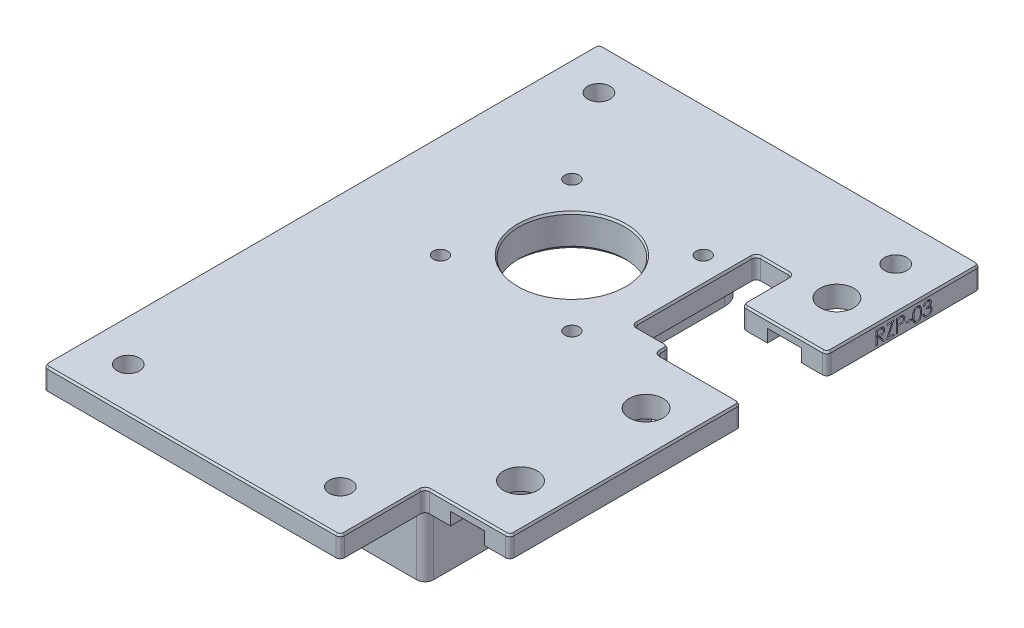
SolidWorks part; units mm, degrees
ref_plane "Front" through (0, 0, 0) normal (0, 0, 1) x (1, 0, 0)
ref_plane "Top" through (0, 0, 0) normal (0, 1, 0) x (1, 0, 0)
ref_plane "Right" through (0, 0, 0) normal (1, 0, 0) x (0, 0, -1)
sketch "Sketch1" plane through (0, 0, 0) normal (0, 1, 0) x (1, 0, 0)
  line L1 (0, 0) -> (90, 0)
  line L2 (0, 0) -> (0, 131)
  line L3 (0, 131) -> (90, 131)
  line L4 (90, 0) -> (90, 131)
  dimension "D1" = 90
  dimension "D2" = 131
extrude "Boss-Extrude1" add sketch "Sketch1" along normal blind 5
sketch "Sketch2" plane through (0, 5, 0) normal (0, 1, 0) x (1, 0, 0)
  line L0 (0, 94.625) -> (20, 94.625)
  line L1 (0, 131) -> (0, 0) construction
  line L2 (20, 94.625) -> (20, 91.625)
  line L3 (20, 91.625) -> (28.5, 91.625)
  line L4 (28.5, 91.625) -> (28.5, 77.625)
  line L5 (28.5, 77.625) -> (20, 77.625)
  line L6 (20, 77.625) -> (20, 74.625)
  line L7 (20, 74.625) -> (0, 74.625)
  line L8 (0, 74.625) -> (0, 94.625)
  line L9 (50, 84.625) -> (56.9971, 84.625) construction
  line L10 (0, 0) -> (20, 0)
  line L11 (0, 0) -> (0, 20)
  line L12 (0, 20) -> (20, 20)
  line L13 (20, 0) -> (20, 20)
  line L15 (90, 131) -> (0, 131) construction
  line L28 (28.5, 106.125) -> (28.5, 91.625) construction
  line L29 (34.5, 69.125) -> (65.5, 69.125) construction
  line L30 (34.5, 69.125) -> (34.5, 100.125) construction
  line L31 (34.5, 100.125) -> (65.5, 100.125) construction
  line L32 (65.5, 69.125) -> (65.5, 100.125) construction
  line L33 (34.5, 69.125) -> (65.5, 100.125) construction
  line L34 (34.5, 100.125) -> (65.5, 69.125) construction
  line L35 (71.5, 63.125) -> (28.5, 63.125) construction
  line L36 (71.5, 63.125) -> (71.5, 106.125) construction
  line L37 (71.5, 106.125) -> (28.5, 106.125) construction
  line L38 (28.5, 63.125) -> (28.5, 106.125) construction
  line L39 (71.5, 63.125) -> (28.5, 106.125) construction
  line L40 (71.5, 106.125) -> (28.5, 63.125) construction
  line L41 (28.5, 77.625) -> (28.5, 63.125) construction
  line L48 (32, 59.625) -> (68, 59.625) construction
  line L49 (32, 59.625) -> (32, 109.625) construction
  line L50 (32, 109.625) -> (68, 109.625) construction
  line L51 (68, 59.625) -> (68, 109.625) construction
  line L52 (32, 59.625) -> (68, 109.625) construction
  line L53 (32, 109.625) -> (68, 59.625) construction
  circle A0 centre (50, 84.625) radius 12.5
  circle A2 centre (65.5, 100.125) radius 1.7
  circle A3 centre (34.5, 100.125) radius 1.7
  circle A4 centre (65.5, 69.125) radius 1.7
  circle A5 centre (34.5, 69.125) radius 1.7
  circle A10 centre (32, 109.625) radius 1.7 construction
  circle A11 centre (68, 109.625) radius 1.7 construction
  circle A12 centre (68, 59.625) radius 1.7 construction
  circle A13 centre (32, 59.625) radius 1.7 construction
  point P14 (28.5, 84.625)
  point P54 (50, 84.625)
  dimension "D5" = 25
  dimension "D9" = 3.4
  dimension "D12" = 3.4
  dimension "D1" = 20
  dimension "D2" = 14
  dimension "D3" = 43
  dimension "D4" = 3
  dimension "D6" = 50
  dimension "D7" = 46.375
  dimension "D8" = 31
  dimension "D10" = 50
  dimension "D11" = 36
  dimension "D13" = 20
extrude "Cut-Extrude1" cut sketch "Sketch2" against normal up to next
hole_wizard "M5 Clearance Hole1" positions "Sketch3" profile "Sketch4" hole size "M5" standard "ANSI Metric" end condition through all
sketch "Sketch3" plane through (0, 5, 0) normal (0, 1, 0) x (1, 0, 0)
  line L0 (10, 20) -> (10, 131) construction
  line L1 (20, 20) -> (0, 20) construction
  line L2 (90, 131) -> (0, 131) construction
  line L5 (20, 10) -> (142.2662, 10) construction
  line L6 (20, 0) -> (20, 20) construction
  line L10 (0, 121) -> (90, 121) construction
  line L11 (0, 131) -> (0, 94.625) construction
  line L12 (90, 0) -> (90, 131) construction
  line L14 (20, 0) -> (90, 0) construction
  line L15 (0, 74.625) -> (0, 20) construction
  line L16 (90, 0) -> (90, 131) construction
  line L17 (90, 111) -> (0, 111) construction
  line L18 (90, 0) -> (90, 131) construction
  line L19 (20, 131) -> (20, 20) construction
  point P31 (10, 121)
  point P37 (80, 121)
  point P42 (30, 10)
  point P45 (80, 10)
  dimension "D1" = 10
  dimension "D2" = 10
  dimension "D3" = 10
  dimension "D4" = 10
  dimension "D5" = 10
  dimension "D6" = 10
  dimension "D7" = 20
sketch "Sketch4" plane through (80, 5, -10) normal (1, 0, 0) x (0, 0, 1)
  line L0 (0, 0) -> (0, 5)
  line L1 (0, 5) -> (2.65, 5)
  line L2 (2.65, 5) -> (2.65, 0)
  line L5 (2.65, 0) -> (0, 0)
  line L11 (0, -6.35) -> (0, 107.95) construction
  dimension "Thru Hole Dia." = 5.3
  dimension "Thru Hole Depth" = 5
sketch "Sketch6" plane through (0, 0, 0) normal (0, -1, 0) x (-1, 0, 0)
  line L0 (-20, 20) -> (0, 20) construction
  line L1 (0, 74.625) -> (-20, 74.625) construction
  line L2 (0, 74.625) -> (0, 20) construction
  line L3 (-20, 94.625) -> (0, 94.625) construction
  line L4 (0, 131) -> (0, 94.625) construction
  circle A0 centre (-10, 32.5) radius 4
  circle A1 centre (-10, 62.125) radius 4
  circle A2 centre (-10, 107.125) radius 4
  dimension "D2" = 8
  dimension "D1" = 12.5
  dimension "D3" = 12.5
  dimension "D4" = 10
  dimension "D5" = 10
  dimension "D6" = 12.5
  dimension "D7" = 10
extrude "Cut-Extrude2" cut sketch "Sketch6" against normal blind 10
other "Move Face1" flip direction yes face at (10, 2.5, -94.625) face at (10, 2.5, -74.625) offset 0.1 parameters "D1"=0.1
sketch "Sketch9" plane through (0, 0, 0) normal (0, -1, 0) x (1, 0, 0)
  line L0 (90, -111) -> (90, -20)
  line L1 (90, 0) -> (90, -131) construction
  line L2 (90, -20) -> (20, -20)
  line L3 (20, -20) -> (20, -74.525)
  line L4 (90, -111) -> (71, -111)
  line L5 (90, -131) -> (0, -131) construction
  line L6 (71, -111) -> (71, -106)
  line L7 (71, -106) -> (85, -106)
  line L8 (85, -106) -> (85, -25)
  line L9 (85, -25) -> (25, -25)
  line L10 (25, -25) -> (25, -74.525)
  line L11 (25, -74.525) -> (20, -74.525)
  line L12 (20, 0) -> (90, 0) construction
  line L13 (0, -74.525) -> (20, -74.525) construction
  line L14 (20, -74.525) -> (20, -77.625) construction
  dimension "D1" = 20
  dimension "D2" = 5
  dimension "D3" = 20
  dimension "D4" = 5
  dimension "D7" = 19
  dimension "D8" = 5
extrude "Boss-Extrude2" add sketch "Sketch9" along normal blind 15
fillet "Fillet4" radius 3 3 edges at (25, -7.5, -25) (85, -7.5, -25) (85, -7.5, -106)
fillet "Fillet5" radius 2 7 edges at (90, -7.5, -20) (90, -7.5, -111) (71, -7.5, -111) (71, -7.5, -106) (20, -7.5, -20) (25, -7.5, -74.525) (20, -7.5, -74.525)
ref_plane "Plane1" through (10, 0, 0) normal (-1, 0, 0) x (0, 0, 1)
sketch "Sketch10" plane through (10, 0, 0) normal (-1, 0, 0) x (0, 0, 1)
  line L0 (-74.525, 0) -> (-74.525, 3)
  line L1 (-28, 0) -> (-103, 0) construction
  line L2 (-74.525, 0) -> (-74.525, 5) construction
  line L3 (-74.525, 3) -> (-71.525, 0)
  line L5 (-71.525, 0) -> (-74.525, 0)
  line L6 (-97.725, 0) -> (-94.725, 0)
  line L8 (-94.725, 0) -> (-94.725, 3)
  line L10 (-94.725, 3) -> (-97.725, 0)
  line L11 (-20, 0) -> (-23, 0)
  line L13 (-20, 0) -> (0, 0) construction
  line L16 (-20, 0) -> (-20, 3)
  line L17 (-20, 0) -> (-20, 5) construction
  line L18 (-20, 3) -> (-23, 0)
  line L21 (-94.725, 0) -> (-94.725, 5) construction
  dimension "D1" = 45
  dimension "D2" = 3
extrude "Cut-Extrude5" cut sketch "Sketch10" against normal blind 4 and the other way blind 4
sketch "Sketch11" plane through (0, 5, 0) normal (0, 1, 0) x (1, 0, 0)
  line L5 (28.5, 77.625) -> (28.5, 91.625) construction
  line L6 (20, 91.625) -> (28.5, 91.625)
  line L7 (20, 91.625) -> (20, 106.625)
  line L8 (20, 106.625) -> (28.5, 106.625)
  line L9 (28.5, 91.625) -> (28.5, 106.625)
  dimension "D1" = 15
extrude "Cut-Extrude6" cut sketch "Sketch11" against normal through all
fillet "Fillet6" radius 1 14 edges at (28.5, 2.5, -77.625) (90, 2.5, 0) (90, 2.5, -131) (0, 2.5, -131) (0, 2.5, -94.725) (20, 2.5, -74.525) (20, 2.5, -77.625) (0, 2.5, -74.525) (0, 2.5, -20) (20, 2.5, 0) (20, 2.5, -20) (28.5, 2.5, -106.625) (20, 2.5, -94.725) (20, 2.5, -106.625)
sketch "Sketch15" plane through (0, 0, 0) normal (0, -1, 0) x (1, 0, 0)
  line L0 (29.5, -100.125) -> (29.5, -69.125)
  line L1 (34.5, -64.125) -> (65.5, -64.125)
  line L2 (70.5, -69.125) -> (70.5, -100.125)
  line L3 (34.5, -105.125) -> (65.5, -105.125)
  circle A0 centre (65.5, -100.125) radius 1.7 construction
  circle A1 centre (34.5, -100.125) radius 1.7 construction
  circle A2 centre (65.5, -69.125) radius 1.7 construction
  circle A3 centre (34.5, -69.125) radius 1.7 construction
  circle A4 centre (65.5, -100.125) radius 1.7
  circle A5 centre (34.5, -100.125) radius 1.7
  circle A6 centre (65.5, -69.125) radius 1.7
  circle A7 centre (34.5, -69.125) radius 1.7
  circle A8 centre (50, -84.625) radius 12.5 construction
  circle A9 centre (50, -84.625) radius 12.5
  circle A10 centre (34.5, -69.125) radius 5 construction
  circle A11 centre (34.5, -100.125) radius 5 construction
  circle A12 centre (65.5, -100.125) radius 5 construction
  circle A13 centre (65.5, -69.125) radius 5 construction
  arc A14 (29.5, -100.125) -> (34.5, -105.125) centre (34.5, -100.125) ccw
  arc A15 (29.5, -69.125) -> (34.5, -64.125) centre (34.5, -69.125) cw
  arc A16 (65.5, -64.125) -> (70.5, -69.125) centre (65.5, -69.125) cw
  arc A17 (70.5, -100.125) -> (65.5, -105.125) centre (65.5, -100.125) cw
  dimension "D1" = 10
extrude "Boss-Extrude3" add sketch "Sketch15" along normal blind 3
chamfer "Chamfer1" distance 1 angle 45 9 edges at (50, -3, -97.125) (70.5, 0, -84.625) (69.0355, 0, -65.5895) (69.0355, 0, -103.6605) (50, 0, -64.125) (50, 0, -105.125) (30.9645, 0, -65.5895) (30.9645, 0, -103.6605) (29.5, 0, -84.625)
chamfer "Printability Chamfer" distance 0.5 angle 30 29 edges at (24.25, 5, -77.625) (20.2929, 5, -77.3321) (28.2071, 5, -77.9179) (20, 5, -76.075) (28.5, 5, -92.125) (19.7071, 5, -74.8179) (28.2071, 5, -106.3321) (10, 5, -74.525) (24.25, 5, -106.625) (0.2929, 5, -74.2321) (20.2929, 5, -106.3321) (0, 5, -47.2625) (20, 5, -100.675) (0.2929, 5, -20.2929) (19.7071, 5, -95.0179) (10, 5, -20) (10, 5, -94.725) (19.7071, 5, -19.7071) (0.2929, 5, -95.0179) (20, 5, -10) (0, 5, -112.8625) (20.2929, 5, -0.2929) (0.2929, 5, -130.7071) (55, 5, 0) (45, 5, -131) (89.7071, 5, -0.2929) (89.7071, 5, -130.7071) (90, 5, -65.5) (50, 5, -72.125) first distance on face at (24.25, 2.5, -77.625) first distance on face at (20.3964, 2.5, -77.2286) first distance on face at (28.1036, 2.5, -78.0214) first distance on face at (20, 2.5, -76.075) first distance on face at (28.5, 2, -93.725) first distance on face at (19.6036, 2.5, -74.9214) first distance on face at (28.1036, 2.5, -106.2286) first distance on face at (10, 2, -74.525) first distance on face at (24.25, 2.5, -106.625) first distance on face at (0.3964, 2.5, -74.1286) first distance on face at (20.3964, 2.5, -106.2286) first distance on face at (0, 2.5, -47.2625) first distance on face at (20, 2.5, -100.675) first distance on face at (0.3964, 2.5, -20.3964) first distance on face at (19.6036, 2.5, -95.1214) first distance on face at (10, 2, -20) first distance on face at (10, 2, -94.725) first distance on face at (19.6036, 2.5, -19.6036) first distance on face at (0.3964, 2.5, -95.1214) first distance on face at (20, 2.5, -10) first distance on face at (0, 2.5, -112.8625) first distance on face at (20.3964, 2.5, -0.3964) first distance on face at (0.3964, 2.5, -130.6036) first distance on face at (55, 2.5, 0) first distance on face at (45, 2.5, -131) first distance on face at (89.6036, 2.5, -0.3964) first distance on face at (89.6036, 2.5, -130.6036) first distance on face at (90, -2.5, -65.5) first distance on face at (50, -2, -97.125)
mirror "Mirror1" about plane through (90, 5, 0) normal (-1, 0, 0) of bodies 114 108
delete or keep bodies "Body-Delete/Keep 1" type delete bodies bodies 114
sketch "Sketch12" [suppressed] plane through (0, 5, 0) normal (1, 0, 0) x (0, -1, 0)
  line L0 (4.4, 131) -> (4.4, 94.825) construction
  line L4 (5, 131) -> (0.5, 131) construction
  line L5 (5, 130) -> (5, 95.825) construction
  line L6 (0.5, 94.825) -> (5, 94.825) construction
  text T0 "LZP-03" font "Century Gothic" height in points 12
  dimension "D1" = 0.6
extrude "Left Part Num" [suppressed] cut sketch "Sketch12" along normal blind 0.4
sketch "Sketch13" plane through (180, -175, 0) normal (-1, 0, 0) x (0, 1, 0)
  line L0 (175.6, 94.725) -> (175.6, 131) construction
  line L4 (175, 131) -> (179.5, 131) construction
  line L5 (179.5, 94.725) -> (175, 94.725) construction
  line L6 (175, 130) -> (175, 95.725) construction
  text T0 "RZP-03" font "Century Gothic" height in points 12
  dimension "D1" = 0.6
extrude "Right Part Num" cut sketch "Sketch13" along normal blind 0.4
equation "\"D3@Sketch6\"=\"D1@Sketch6\""
equation "\"D6@Sketch6\"=\"D1@Sketch6\""
equation "\"D8@Sketch9\"=\"D4@Sketch9\""
equation "\"D2@Sketch9\"=\"D4@Sketch9\""
